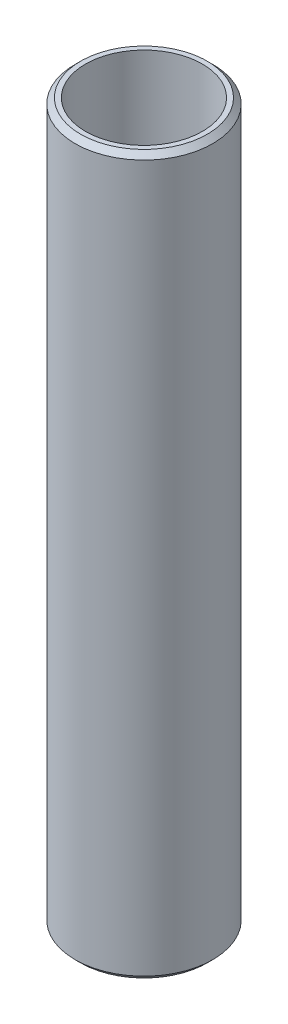
SolidWorks part; units mm, degrees
ref_plane "Front Plane" through (0, 0, 0) normal (0, 0, 1) x (1, 0, 0)
ref_plane "Top Plane" through (0, 0, 0) normal (0, 1, 0) x (1, 0, 0)
ref_plane "Right Plane" through (0, 0, 0) normal (1, 0, 0) x (0, 0, -1)
sketch "Sketch1" plane through (0, 0, 0) normal (0, 1, 0) x (1, 0, 0)
  circle A0 centre (0, 0) radius 57.5
  dimension "SHAFT_OD" = 115
extrude "Boss-Extrude1" add sketch "Sketch1" along normal blind 600
sketch "Sketch2" plane through (0, 0, 0) normal (0, 1, 0) x (1, 0, 0)
  circle A0 centre (0, 0) radius 48.8581
  dimension "BORE_D" = 97.7162
extrude "Cut-Extrude1" cut sketch "Sketch2" along normal through all
chamfer "Chamfer1" distance 4.5398 angle 45 2 edges at (0, 600, 57.5) (0, 0, 57.5)
